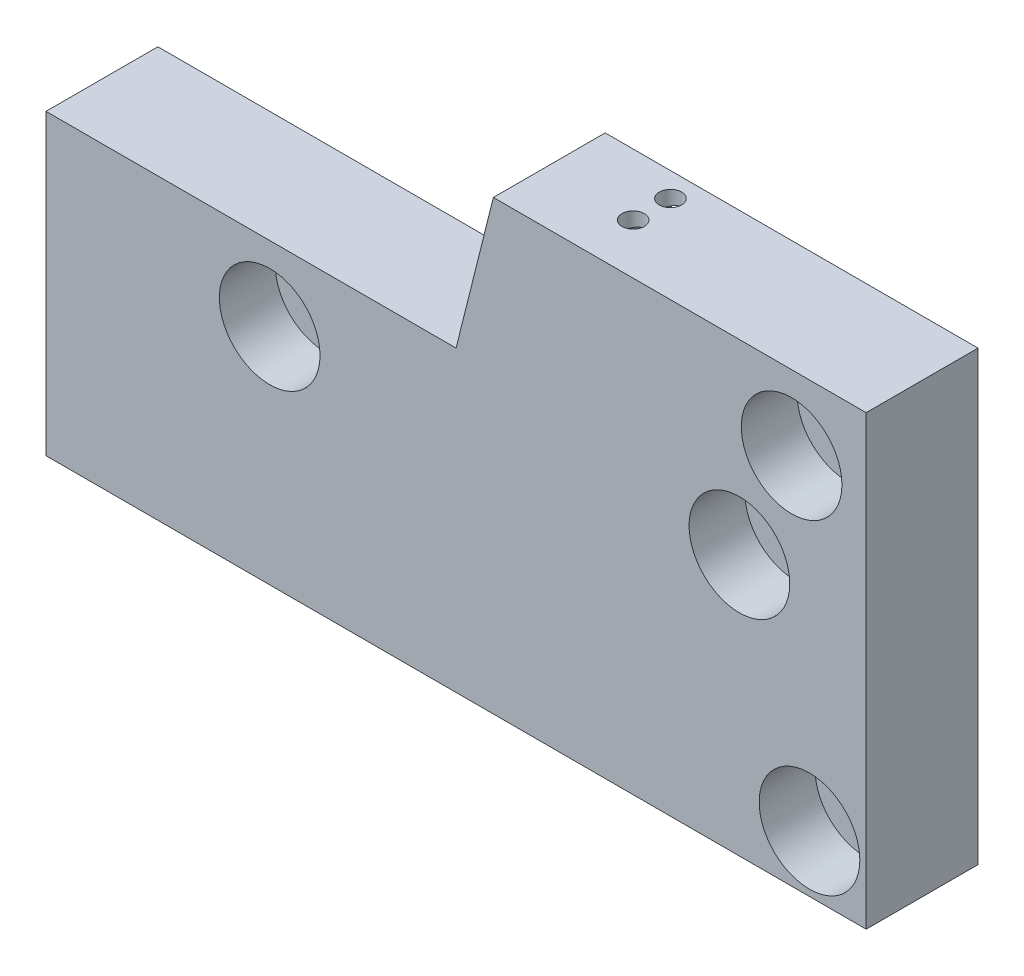
SolidWorks part; units mm, degrees
ref_plane "Front Plane" through (0, 0, 0) normal (0, 0, 1) x (1, 0, 0)
ref_plane "Top Plane" through (0, 0, 0) normal (0, 1, 0) x (1, 0, 0)
ref_plane "Right Plane" through (0, 0, 0) normal (1, 0, 0) x (0, 0, -1)
sketch "Sketch1" plane through (0, 0, 0) normal (0, 0, 1) x (1, 0, 0)
  line L9 (0, 0) -> (110, 0)
  line L10 (110, 0) -> (110, 60)
  line L11 (110, 60) -> (60, 60)
  line L12 (60, 60) -> (55, 40)
  line L13 (55, 40) -> (0, 40)
  line L14 (0, -50) -> (0, 50) construction
  line L15 (0, 40) -> (0, 0)
  circle A0 centre (72, 55) radius 3
  circle A1 centre (81, 5) radius 3
  circle A2 centre (93, 35) radius 3
  circle A3 centre (30, 30) radius 3
  circle A4 centre (100, 50) radius 3
  circle A5 centre (102.4, 7.6) radius 3
  dimension "D6" = 6
  dimension "D7" = 6
  dimension "D12" = 6
  dimension "D15" = 6
  dimension "D19" = 6
  dimension "D20" = 6
  dimension "D1" = 110
  dimension "D2" = 60
  dimension "D3" = 40
  dimension "D4" = 55
  dimension "D5" = 50
  dimension "D8" = 5
  dimension "D9" = 12
  dimension "D10" = 5
  dimension "D11" = 21
  dimension "D13" = 35
  dimension "D14" = 17
  dimension "D16" = 30
  dimension "D17" = 30
  dimension "D23" = 7.6
  dimension "D24" = 7.6
  dimension "D25" = 10
  dimension "D26" = 10
extrude "Boss-Extrude1" add sketch "Sketch1" against normal blind 15 contours L13 L15 L9 L10 L11 L12
extrude "Cut-Extrude1" cut sketch "Sketch1<4>" against normal blind 15 contours A2 | A3
sketch "Sketch1<4>" plane through (0, 0, 0) normal (0, 0, 1) x (1, 0, 0) same geometry as "Sketch1"
extrude "Cut-Extrude2" cut sketch "Sketch1<5>" against normal blind 15 contours A4 | A5
sketch "Sketch1<5>" plane through (0, 0, 0) normal (0, 0, 1) x (1, 0, 0) same geometry as "Sketch1"
sketch "Sketch2" plane through (0, 0, -15) normal (0, 0, -1) x (-1, 0, 0)
  circle A0 centre (-72, 55) radius 3.25
  circle A1 centre (-81, 5) radius 3.25
  dimension "D1" = 6.5
  dimension "D2" = 6.5
extrude "Cut-Extrude3" cut sketch "Sketch2" against normal blind 13
sketch "Sketch3" plane through (0, 0, 0) normal (0, 0, 1) x (1, 0, 0)
  line L1 (106.3509, 50) -> (103.1754, 55.5)
  line L2 (103.1754, 55.5) -> (96.8246, 55.5)
  line L3 (96.8246, 55.5) -> (93.6491, 50)
  line L4 (93.6491, 50) -> (96.8246, 44.5)
  line L5 (96.8246, 44.5) -> (103.1754, 44.5)
  line L6 (103.1754, 44.5) -> (106.3509, 50)
  line L7 (86.6491, 35) -> (89.8246, 29.5)
  line L8 (96.1754, 29.5) -> (99.3509, 35)
  line L9 (99.3509, 35) -> (96.1754, 40.5)
  line L10 (89.8246, 40.5) -> (86.6491, 35)
  line L11 (89.8246, 29.5) -> (96.1754, 29.5)
  line L12 (96.1754, 40.5) -> (89.8246, 40.5)
  line L13 (105.5754, 13.1) -> (99.2246, 13.1)
  line L14 (108.7509, 7.6) -> (105.5754, 13.1)
  line L15 (105.5754, 2.1) -> (108.7509, 7.6)
  line L16 (96.0491, 7.6) -> (99.2246, 2.1)
  line L17 (99.2246, 13.1) -> (96.0491, 7.6)
  line L18 (99.2246, 2.1) -> (105.5754, 2.1)
  circle A0 centre (100, 50) radius 6.75
  circle A7 centre (100, 50) radius 5.5 construction
  circle A8 centre (93, 35) radius 5.5 construction
  circle A9 centre (93, 35) radius 6.75
  circle A10 centre (102.4, 7.6) radius 5.5 construction
  circle A11 centre (102.4, 7.6) radius 6.75
  circle A16 centre (30, 30) radius 6.75
  dimension "D1" = 13.5
  dimension "D3" = 13.5
  dimension "D4" = 13.5
  dimension "D5" = 13.5
  dimension "D2" = 11
extrude "Cut-Extrude4" cut sketch "Sketch3" against normal blind 7.5 contours A9 | A0 | A16 | A11
sketch "Sketch5" plane through (0, 60, 0) normal (0, 1, 0) x (1, 0, 0)
  line L0 (68.75, 15) -> (75.8876, 15) construction
  line L1 (0, 15) -> (110, 15) construction
  line L2 (75.25, 15) -> (68.75, 15) construction
  line L3 (72, 2) -> (72, 18.1718) construction
  line L4 (75.25, 2) -> (68.75, 2) construction
  circle A0 centre (72, 11.75) radius 1.5
  circle A1 centre (72, 6.75) radius 1.5
  dimension "D2" = 3
  dimension "D4" = 3
  dimension "D1" = 3.25
  dimension "D3" = 8.25
extrude "Cut-Extrude5" cut sketch "Sketch5" against normal blind 10
sketch "Sketch6" plane through (0, 0, 0) normal (0, -1, 0) x (1, 0, 0)
  line L0 (86.2495, -15) -> (73.0766, -15) construction
  line L1 (110, -15) -> (60, -15) construction
  line L2 (68.75, -15) -> (75.25, -15) construction
  line L3 (81, -2) -> (81, -16.7497) construction
  line L4 (77.75, -2) -> (84.25, -2) construction
  circle A0 centre (81, -6.75) radius 1.5
  circle A1 centre (81, -11.75) radius 1.5
  dimension "3" = 3
  dimension "D2" = 3
  dimension "D3" = 3.25
  dimension "D4" = 8.25
extrude "Cut-Extrude6" cut sketch "Sketch6" against normal blind 10
